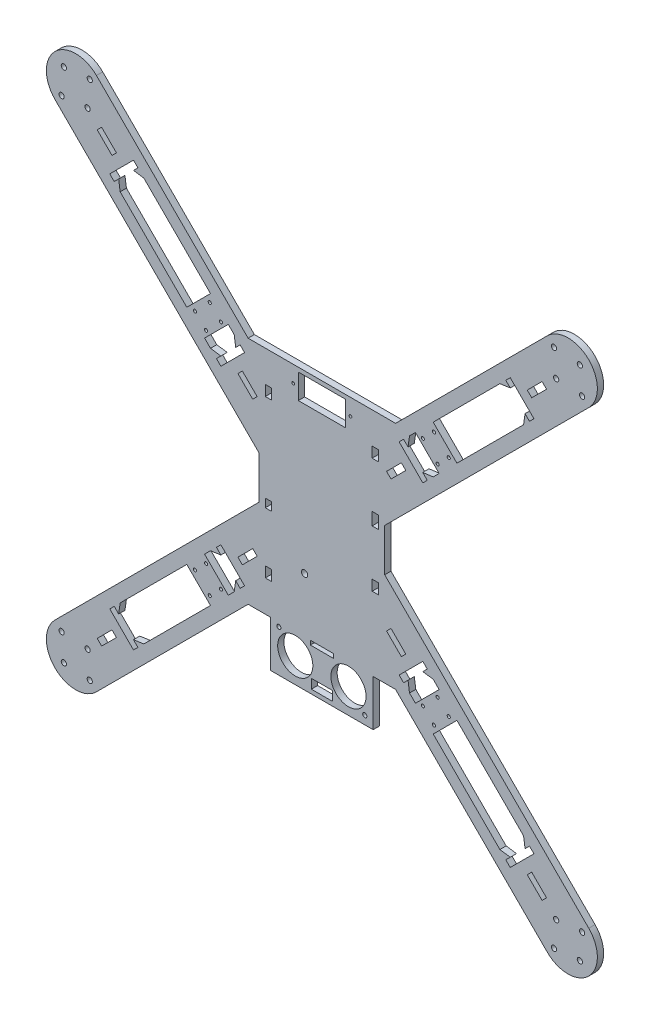
SolidWorks part; units mm, degrees
material "Custom Plastic"
ref_plane "Front Plane" through (0, 0, 0) normal (0, 0, 1) x (1, 0, 0)
ref_plane "Top Plane" through (0, 0, 0) normal (0, 1, 0) x (1, 0, 0)
ref_plane "Right Plane" through (0, 0, 0) normal (1, 0, 0) x (0, 0, -1)
sketch "Sketch1" plane through (0, 0, 0) normal (0, 0, 1) x (1, 0, 0)
  line L0 (117.5, 117.5) -> (-117.5, 117.5) construction
  line L1 (-117.5, 117.5) -> (117.5, -117.5) construction
  line L2 (117.5, -117.5) -> (-117.5, -117.5) construction
  line L3 (-117.5, -117.5) -> (117.5, 117.5) construction
  line L4 (117.5, 117.5) -> (117.5, -117.5) construction
  line L5 (-117.5, 117.5) -> (-117.5, -117.5) construction
  line L6 (0, 117.5) -> (0, -117.5) construction
  line L7 (35.201, 55) -> (-35.201, 55)
  line L8 (-30, 55) -> (30, 55) construction
  line L9 (-35.201, 55) -> (-107.6005, 127.3995)
  line L10 (-127.3995, 107.6005) -> (-30, 10.201)
  line L11 (-117.5, 0) -> (117.5, 0) construction
  line L12 (-30, 10.201) -> (-30, -10.201)
  line L13 (30, 55) -> (30, -55) construction
  line L14 (30, -55) -> (-30, -55) construction
  line L15 (-30, -55) -> (-30, 55) construction
  line L16 (30, 55) -> (-30, -55) construction
  line L17 (-24.5, -55) -> (-24.5, -77)
  line L18 (-127.3995, -107.6005) -> (-30, -10.201)
  line L19 (-24.5, -77) -> (24.5, -77)
  line L20 (-35.201, -55) -> (-107.6005, -127.3995)
  line L21 (35.201, -55) -> (24.5, -55)
  line L22 (35.201, -55) -> (107.6005, -127.3995)
  line L23 (127.3995, -107.6005) -> (30, -10.201)
  line L24 (30, 10.201) -> (30, -10.201)
  line L25 (127.3995, 107.6005) -> (30, 10.201)
  line L26 (35.201, 55) -> (107.6005, 127.3995)
  line L27 (24.5, -55) -> (24.5, -77)
  line L28 (-24.5, -55) -> (-35.201, -55)
  arc A0 (-107.6005, 127.3995) -> (-127.3995, 107.6005) centre (-117.5, 117.5) ccw
  arc A12 (-107.6005, -127.3995) -> (-127.3995, -107.6005) centre (-117.5, -117.5) cw
  arc A16 (107.6005, -127.3995) -> (127.3995, -107.6005) centre (117.5, -117.5) ccw
  arc A24 (107.6005, 127.3995) -> (127.3995, 107.6005) centre (117.5, 117.5) cw
  point P3 (0, 0)
  point P18 (0, 0)
  point P21 (0, -77)
  point P33 (-117.5, 117.5)
  point P34 (-30, 0)
  point P65 (0, -55)
  point P80 (0, 55)
  dimension "D3" = 14
  dimension "D8" = 24.5
  dimension "D7" = 22
  dimension "D1" = 235
  dimension "D2" = 235
  dimension "D4" = 60
  dimension "D5" = 110
  dimension "D6" = 28
extrude "Boss-Extrude1" add sketch "Sketch1" against normal blind 3
sketch "Sketch4" plane through (0, 0, 0) normal (0, 0, 1) x (1, 0, 0)
  line L0 (0, 0) -> (0, 55) construction
  line L1 (35.201, 55) -> (-35.201, 55) construction
  line L2 (0, 0) -> (-30, 0) construction
  line L3 (-30, 10.201) -> (-30, -10.201) construction
  line L4 (-30, 0) -> (-30, 10.201) construction
  line L5 (-30, 10.201) -> (-127.3995, 107.6005) construction
  line L6 (-35.201, 55) -> (-107.6005, 127.3995) construction
  line L7 (-107.6005, 127.3995) -> (-127.3995, 107.6005) construction
  line L8 (-110.7825, 124.2175) -> (-124.2175, 110.7825) construction
  line L9 (-123.1569, 123.1569) -> (-111.8431, 111.8431) construction
  circle A20 centre (-110.7825, 124.2175) radius 1.25
  circle A21 centre (-124.2175, 110.7825) radius 1.25
  circle A22 centre (-123.1569, 123.1569) radius 1.25
  circle A23 centre (-111.8431, 111.8431) radius 1.25
  circle A24 centre (111.8431, 111.8431) radius 1.25
  circle A25 centre (110.7825, 124.2175) radius 1.25
  circle A26 centre (123.1569, 123.1569) radius 1.25
  circle A27 centre (124.2175, 110.7825) radius 1.25
  circle A28 centre (111.8431, -111.8431) radius 1.25
  circle A29 centre (124.2175, -110.7825) radius 1.25
  circle A30 centre (123.1569, -123.1569) radius 1.25
  circle A31 centre (110.7825, -124.2175) radius 1.25
  circle A32 centre (-111.8431, -111.8431) radius 1.25
  circle A33 centre (-110.7825, -124.2175) radius 1.25
  circle A34 centre (-123.1569, -123.1569) radius 1.25
  circle A35 centre (-124.2175, -110.7825) radius 1.25
  point P16 (-117.5, 117.5)
  point P19 (-117.5, 117.5)
  point P26 (-117.5, 117.5)
  point P62 (0, 0)
  dimension "D4" = 2.5
  dimension "D2" = 19
  dimension "D3" = 16
extrude "Cut-Extrude1" cut sketch "Sketch4" against normal blind 3
sketch "Sketch5" plane through (0, 0, 0) normal (0, 0, 1) x (1, 0, 0)
  line L7 (-11.25, 53) -> (-11.25, 41.2)
  line L8 (-11.25, 41.2) -> (11.25, 41.2)
  line L9 (11.25, 41.2) -> (11.25, 53)
  line L10 (11.25, 53) -> (-11.25, 53)
  line L12 (0, 53) -> (0, 41.2) construction
  line L13 (-13.65, 47.1) -> (13.65, 47.1) construction
  line L14 (35.201, 55) -> (-35.201, 55) construction
  circle A2 centre (-13.65, 47.1) radius 0.65
  circle A3 centre (13.65, 47.1) radius 0.65
  point P20 (0, 47.1)
  point P21 (0, 47.1)
  point P26 (0, 55)
  dimension "D8" = 1.3
  dimension "D9" = 1.3
  dimension "D10" = 27.3
  dimension "D11" = 22.5
  dimension "D12" = 11.8
  dimension "D13" = 2
extrude "Cut-Extrude2" cut sketch "Sketch5" against normal blind 3
sketch "Sketch6" plane through (0, 0, 0) normal (0, 0, 1) x (1, 0, 0)
  line L1 (-11.25, 41.2) -> (11.25, 41.2) construction
  circle A0 centre (-8.25, -28.8) radius 1.5
  dimension "D3" = 3
  dimension "D1" = 70
  dimension "D2" = 3
extrude "Cut-Extrude3" cut sketch "Sketch6" against normal blind 3
sketch "Sketch7" plane through (0, 0, 0) normal (0, 0, 1) x (1, 0, 0)
  line L0 (-22.5, -55) -> (-22.5, -75) construction
  line L5 (-22.5, -75) -> (22.5, -75) construction
  line L6 (22.5, -75) -> (22.5, -55) construction
  line L7 (22.5, -55) -> (-22.5, -55) construction
  line L8 (0, -55) -> (0, -75) construction
  line L9 (-12.7, -65) -> (0, -65) construction
  line L10 (-24.5, -77) -> (24.5, -77) construction
  line L11 (-24.5, -55) -> (-24.5, -77) construction
  line L12 (-5.5, -55) -> (-5.5, -57)
  line L13 (-5.5, -57) -> (5.5, -57)
  line L15 (5.5, -55) -> (-5.5, -55)
  line L16 (-5, -75) -> (-5, -70.5)
  line L17 (-5, -70.5) -> (5, -70.5)
  line L21 (5, -75) -> (-5, -75)
  line L22 (5.5, -55) -> (5.5, -57)
  line L23 (5, -75) -> (5, -70.5)
  circle A5 centre (-20.5, -57) radius 1
  circle A6 centre (-12.7, -65) radius 8.4
  circle A7 centre (12.7, -65) radius 8.4
  circle A8 centre (20.5, -73) radius 1
  point P25 (0, -57)
  point P26 (0, -70.5)
  dimension "D3" = 2
  dimension "D6" = 20
  dimension "D13" = 5
  dimension "D5" = 45
  dimension "D1" = 2
  dimension "D4" = 16.8
  dimension "D14" = 2
  dimension "D2" = 2
  dimension "D7" = 2
  dimension "D8" = 2
  dimension "D9" = 12.7
  dimension "D10" = 5.5
  dimension "D11" = 2
  dimension "D12" = 4.5
  dimension "D15" = 2
  dimension "D16" = 2
extrude "Cut-Extrude4" cut sketch "Sketch7" against normal blind 3
sketch "Sketch8" plane through (0, 0, 0) normal (0, 0, 1) x (1, 0, 0)
  line L0 (101.2365, -89.9228) -> (89.9228, -101.2365)
  line L1 (89.9228, -101.2365) -> (87.8015, -99.1152)
  line L2 (36.8898, -48.2035) -> (48.2035, -36.8898)
  line L3 (48.2035, -36.8898) -> (50.3249, -39.0111)
  line L4 (105.4792, -85.6802) -> (85.6802, -105.4792) construction
  line L5 (127.3995, -107.6005) -> (30, -10.201) construction
  line L6 (35.201, -55) -> (107.6005, -127.3995) construction
  line L7 (40.0718, -37.9505) -> (37.9505, -40.0718)
  line L8 (115.8431, -107.8431) -> (111.8431, -111.8431) construction
  line L9 (37.9505, -40.0718) -> (30.8794, -33.0007)
  line L10 (50.3249, 39.0111) -> (48.2035, 36.8898)
  line L11 (30.8794, -33.0007) -> (33.0007, -30.8794)
  line L12 (33.0007, -30.8794) -> (40.0718, -37.9505)
  line L13 (42.5467, -42.5467) -> (39.0111, -39.0111) construction
  line L14 (35.201, -55) -> (107.6005, -127.3995) construction
  line L15 (100.1759, -98.0546) -> (98.0546, -100.1759)
  line L16 (98.0546, -100.1759) -> (105.1256, -107.247)
  line L17 (105.1256, -107.247) -> (107.247, -105.1256)
  line L18 (107.247, -105.1256) -> (100.1759, -98.0546)
  line L19 (99.1152, -99.1152) -> (95.5797, -95.5797) construction
  line L20 (-101.2365, -89.9228) -> (-99.1152, -87.8015)
  line L21 (-100.1759, -98.0546) -> (-107.247, -105.1256)
  line L22 (-107.247, -105.1256) -> (-105.1256, -107.247)
  line L23 (-105.1256, -107.247) -> (-98.0546, -100.1759)
  line L24 (-98.0546, -100.1759) -> (-100.1759, -98.0546)
  line L25 (-89.9228, -101.2365) -> (-101.2365, -89.9228)
  line L26 (-36.8898, -48.2035) -> (-39.0111, -50.3249)
  line L27 (-48.2035, -36.8898) -> (-36.8898, -48.2035)
  line L28 (-37.9505, -40.0718) -> (-40.0718, -37.9505)
  line L29 (-30.8794, -33.0007) -> (-37.9505, -40.0718)
  line L30 (-40.0718, -37.9505) -> (-33.0007, -30.8794)
  line L31 (-33.0007, -30.8794) -> (-30.8794, -33.0007)
  line L32 (-89.9228, 101.2365) -> (-87.8015, 99.1152)
  line L33 (-98.0546, 100.1759) -> (-105.1256, 107.247)
  line L34 (-105.1256, 107.247) -> (-107.247, 105.1256)
  line L35 (-107.247, 105.1256) -> (-100.1759, 98.0546)
  line L36 (-100.1759, 98.0546) -> (-98.0546, 100.1759)
  line L37 (-101.2365, 89.9228) -> (-89.9228, 101.2365)
  line L38 (-48.2035, 36.8898) -> (-50.3249, 39.0111)
  line L39 (-36.8898, 48.2035) -> (-48.2035, 36.8898)
  line L40 (-40.0718, 37.9505) -> (-37.9505, 40.0718)
  line L41 (-33.0007, 30.8794) -> (-40.0718, 37.9505)
  line L42 (-37.9505, 40.0718) -> (-30.8794, 33.0007)
  line L43 (-30.8794, 33.0007) -> (-33.0007, 30.8794)
  line L44 (101.2365, 89.9228) -> (99.1152, 87.8015)
  line L45 (100.1759, 98.0546) -> (107.247, 105.1256)
  line L46 (107.247, 105.1256) -> (105.1256, 107.247)
  line L47 (105.1256, 107.247) -> (98.0546, 100.1759)
  line L48 (98.0546, 100.1759) -> (100.1759, 98.0546)
  line L49 (89.9228, 101.2365) -> (101.2365, 89.9228)
  line L50 (36.8898, 48.2035) -> (39.0111, 50.3249)
  line L51 (48.2035, 36.8898) -> (36.8898, 48.2035)
  line L52 (37.9505, 40.0718) -> (40.0718, 37.9505)
  line L53 (30.8794, 33.0007) -> (37.9505, 40.0718)
  line L54 (40.0718, 37.9505) -> (33.0007, 30.8794)
  line L55 (33.0007, 30.8794) -> (30.8794, 33.0007)
  line L56 (30, 10.201) -> (127.3995, 107.6005) construction
  line L57 (41.8396, 53.1533) -> (84.9731, 96.2868)
  line L58 (96.2868, 84.9731) -> (53.1533, 41.8396)
  line L59 (87.8015, 99.1152) -> (89.9228, 101.2365)
  line L60 (99.1152, -87.8015) -> (96.9939, -89.9228)
  line L61 (-96.2868, -84.9731) -> (-53.1533, -41.8396)
  line L62 (96.9939, -89.9228) -> (96.2868, -84.9731)
  line L63 (99.1152, -87.8015) -> (101.2365, -89.9228)
  line L64 (87.8015, -99.1152) -> (89.9228, -96.9939)
  line L65 (-87.8015, -99.1152) -> (-89.9228, -101.2365)
  line L66 (89.9228, -96.9939) -> (84.9731, -96.2868)
  line L67 (84.9731, -96.2868) -> (41.8396, -53.1533)
  line L68 (50.3249, -39.0111) -> (48.2035, -41.1325)
  line L69 (48.2035, -41.1325) -> (53.1533, -41.8396)
  line L70 (53.1533, -41.8396) -> (96.2868, -84.9731)
  line L71 (39.0111, -50.3249) -> (41.1325, -48.2035)
  line L72 (41.1325, -48.2035) -> (41.8396, -53.1533)
  line L73 (39.0111, -50.3249) -> (36.8898, -48.2035)
  line L74 (-89.9228, -96.9939) -> (-84.9731, -96.2868)
  line L75 (-87.8015, -99.1152) -> (-89.9228, -96.9939)
  line L76 (-96.9939, -89.9228) -> (-96.2868, -84.9731)
  line L77 (-99.1152, -87.8015) -> (-96.9939, -89.9228)
  line L78 (-41.1325, -48.2035) -> (-41.8396, -53.1533)
  line L79 (-39.0111, -50.3249) -> (-41.1325, -48.2035)
  line L80 (-48.2035, -41.1325) -> (-53.1533, -41.8396)
  line L81 (-50.3249, -39.0111) -> (-48.2035, -41.1325)
  line L82 (-96.9939, 89.9228) -> (-96.2868, 84.9731)
  line L83 (-99.1152, 87.8015) -> (-96.9939, 89.9228)
  line L84 (-89.9228, 96.9939) -> (-84.9731, 96.2868)
  line L85 (-87.8015, 99.1152) -> (-89.9228, 96.9939)
  line L86 (-48.2035, 41.1325) -> (-53.1533, 41.8396)
  line L87 (-50.3249, 39.0111) -> (-48.2035, 41.1325)
  line L88 (-41.1325, 48.2035) -> (-41.8396, 53.1533)
  line L89 (-39.0111, 50.3249) -> (-41.1325, 48.2035)
  line L90 (89.9228, 96.9939) -> (84.9731, 96.2868)
  line L91 (87.8015, 99.1152) -> (89.9228, 96.9939)
  line L92 (96.9939, 89.9228) -> (96.2868, 84.9731)
  line L93 (99.1152, 87.8015) -> (96.9939, 89.9228)
  line L94 (41.1325, 48.2035) -> (41.8396, 53.1533)
  line L95 (39.0111, 50.3249) -> (41.1325, 48.2035)
  line L96 (48.1429, 41.1931) -> (53.1533, 41.8396)
  line L97 (50.3249, 39.0111) -> (48.1429, 41.1931)
  line L98 (-39.0111, 50.3249) -> (-36.8898, 48.2035)
  line L99 (-53.1533, 41.8396) -> (-96.2868, 84.9731)
  line L100 (-99.1152, 87.8015) -> (-101.2365, 89.9228)
  line L101 (-84.9731, 96.2868) -> (-41.8396, 53.1533)
  line L102 (-41.8396, -53.1533) -> (-84.9731, -96.2868)
  line L103 (-50.3249, -39.0111) -> (-48.2035, -36.8898)
  line L104 (96.2868, 84.9731) -> (84.9731, 96.2868) construction
  line L105 (53.1533, 41.8396) -> (41.8396, 53.1533) construction
  point P10 (95.5797, -95.5797)
  point P11 (95.5797, -95.5797)
  point P18 (-49.2642, 40.0718)
  point P19 (-49.2642, -40.0718)
  point P68 (0, 0)
  point P122 (0, 0)
  dimension "D1" = 23
  dimension "D2" = 75
  dimension "D3" = 3
  dimension "D4" = 10
  dimension "D5" = 5
  dimension "D6" = 6
  dimension "D7" = 3
  dimension "D8" = 10
  dimension "D9" = 5
  dimension "D11" = 6
  dimension "D12" = 3
  dimension "D13" = 4
  dimension "D14" = 3
  dimension "D15" = 3
  dimension "D16" = 4
  dimension "D17" = 3
  dimension "D18" = 3
  dimension "D19" = 4
  dimension "D20" = 3
  dimension "D21" = 3
  dimension "D22" = 4
  dimension "D23" = 3
  dimension "D24" = 3
  dimension "D25" = 4
  dimension "D26" = 3
  dimension "D27" = 4
  dimension "D28" = 3
  dimension "D29" = 3
  dimension "D30" = 4
  dimension "D31" = 4
  dimension "D32" = 3
  dimension "D33" = 3
  dimension "D34" = 4
  dimension "D35" = 4
  dimension "D36" = 3
  dimension "D37" = 3
  dimension "D38" = 4
  dimension "D39" = 4
  dimension "D40" = 3
  dimension "D41" = 3
  dimension "D42" = 4
  dimension "D43" = 4
  dimension "D10" = 4
extrude "Cut-Extrude5" cut sketch "Sketch8" against normal through all
sketch "Sketch9" plane through (-5.6569, 5.6569, 0) normal (0.7071, -0.7071, 0) x (0, 0, -1)
  line L0 (3, 128.1701) -> (3, 67.1701) construction
  line L1 (3, 83.1701) -> (0, 83.1701)
  line L2 (3, 83.1701) -> (3, 71.1701)
  line L3 (3, 71.1701) -> (0, 71.1701)
  line L4 (0, 83.1701) -> (0, 71.1701)
  line L5 (0, 128.1701) -> (0, 67.1701) construction
  line L6 (0, 0) -> (28.0274, 0) construction
  line L7 (3, 63.1701) -> (0, 63.1701) construction
  dimension "D1" = 8
  dimension "D2" = 12
extrude "Boss-Extrude2" add sketch "Sketch9" along normal up to next
sketch "Sketch11" plane through (5.6569, 5.6569, 0) normal (-0.7071, -0.7071, 0) x (0, 0, 1)
  line L0 (-3, -128.1701) -> (-3, -67.1701) construction
  line L1 (-3, -71.1701) -> (0, -71.1701)
  line L2 (-3, -71.1701) -> (-3, -83.1701)
  line L3 (-3, -83.1701) -> (0, -83.1701)
  line L4 (0, -71.1701) -> (0, -83.1701)
  line L5 (0, -128.1701) -> (0, -67.1701) construction
  line L6 (-3, -63.1701) -> (0, -63.1701) construction
  dimension "D1" = 8
  dimension "D2" = 12
extrude "Boss-Extrude3" add sketch "Sketch11" along normal up to next
sketch "Sketch12" plane through (5.6569, -5.6569, 0) normal (-0.7071, 0.7071, 0) x (0, 0, 1)
  line L0 (-3, -128.1701) -> (-3, -67.1701) construction
  line L1 (-3, -71.1701) -> (0, -71.1701)
  line L2 (-3, -71.1701) -> (-3, -83.1701)
  line L3 (-3, -83.1701) -> (0, -83.1701)
  line L4 (0, -71.1701) -> (0, -83.1701)
  line L5 (0, -128.1701) -> (0, -67.1701) construction
  dimension "D1" = 8
  dimension "D2" = 12
extrude "Boss-Extrude4" add sketch "Sketch12" along normal up to next
sketch "Sketch13" plane through (5.6569, 5.6569, 0) normal (-0.7071, -0.7071, 0) x (0, 0, 1)
  line L0 (-3, 67.1701) -> (-3, 128.1701) construction
  line L1 (-3, 71.1701) -> (0, 71.1701)
  line L2 (-3, 71.1701) -> (-3, 83.1701)
  line L3 (-3, 83.1701) -> (0, 83.1701)
  line L4 (0, 71.1701) -> (0, 83.1701)
  line L5 (0, 67.1701) -> (0, 128.1701) construction
  dimension "D1" = 8
  dimension "D2" = 12
extrude "Boss-Extrude5" add sketch "Sketch13" along normal up to next
sketch "Sketch14" plane through (0, 0, -3) normal (0, 0, -1) x (-1, 0, 0)
  line L0 (30, 0) -> (-30, 0) construction
  line L1 (30, 10.201) -> (30, -10.201) construction
  line L2 (-30, -10.201) -> (-30, 10.201) construction
  line L3 (25.5, -40) -> (25.5, 40) construction
  line L12 (24, -35) -> (-25.5, -35) construction
  line L13 (-25.5, -35) -> (-25.5, -15) construction
  line L14 (-24, 13) -> (-24, 7)
  line L17 (-24, 7) -> (-27, 7)
  line L19 (-24, 13) -> (-27, 13)
  line L23 (24, -40) -> (27, -40)
  line L24 (24, -40) -> (24, -35)
  line L25 (24, -35) -> (27, -35)
  line L26 (27, -40) -> (27, -35)
  line L27 (24, -11) -> (27, -11)
  line L28 (24, -11) -> (24, -7)
  line L29 (24, -7) -> (27, -7)
  line L30 (27, -11) -> (27, -7)
  line L31 (24, 35) -> (27, 35)
  line L32 (24, 35) -> (24, 40)
  line L33 (24, 40) -> (27, 40)
  line L34 (27, 35) -> (27, 40)
  line L35 (-27, 13) -> (-27, 7)
  line L37 (-24, -20) -> (-27, -20)
  line L38 (-24, -20) -> (-24, -15)
  line L39 (-24, -15) -> (-27, -15)
  line L40 (-27, -20) -> (-27, -15)
  line L41 (-24, 35) -> (-27, 35)
  line L42 (-24, 35) -> (-24, 40)
  line L43 (-24, 40) -> (-27, 40)
  line L44 (-27, 35) -> (-27, 40)
  point P11 (25.5, -40)
  point P16 (25.5, 0)
  point P28 (-25.5, 13)
  point P38 (-25.5, 7)
  dimension "D1" = 80
  dimension "D2" = 3
  dimension "D3" = 5
  dimension "D4" = 24
  dimension "D5" = 20
  dimension "D6" = 22
  dimension "D7" = 6
  dimension "D8" = 5
  dimension "D9" = 22
  dimension "D10" = 4
  dimension "D11" = 5
  dimension "D12" = 42
  dimension "D13" = 5
extrude "Cut-Extrude6" cut sketch "Sketch14" against normal through all
sketch "Sketch15" plane through (0, 0, -3) normal (0, 0, -1) x (-1, 0, 0)
  line L0 (-55.2746, -48.2035) -> (-48.2035, -55.2746) construction
  line L1 (-48.2035, -55.2746) -> (-53.5068, -60.5779) construction
  line L2 (-53.5068, -60.5779) -> (-60.5779, -53.5068) construction
  line L3 (-60.5779, -53.5068) -> (-55.2746, -48.2035) construction
  line L4 (-64.2902, -44.4912) -> (-44.4912, -64.2902) construction
  line L5 (-127.3995, -107.6005) -> (-30, -10.201) construction
  line L6 (-35.201, -55) -> (-107.6005, -127.3995) construction
  line L7 (-57.0424, -57.0424) -> (-51.7391, -51.7391) construction
  line L8 (-53.1533, -64.467) -> (-64.467, -53.1533) construction
  circle A6 centre (-60.5779, -53.5068) radius 0.75
  circle A7 centre (-55.2746, -48.2035) radius 0.75
  circle A8 centre (-48.2035, -55.2746) radius 0.75
  circle A9 centre (-53.5068, -60.5779) radius 0.75
  circle A10 centre (-53.5068, 60.5779) radius 0.75
  circle A11 centre (-48.2035, 55.2746) radius 0.75
  circle A12 centre (-60.5779, 53.5068) radius 0.75
  circle A13 centre (-55.2746, 48.2035) radius 0.75
  circle A14 centre (60.5779, 53.5068) radius 0.75
  circle A15 centre (55.2746, 48.2035) radius 0.75
  circle A16 centre (53.5068, 60.5779) radius 0.75
  circle A17 centre (48.2035, 55.2746) radius 0.75
  circle A18 centre (53.5068, -60.5779) radius 0.75
  circle A19 centre (48.2035, -55.2746) radius 0.75
  circle A20 centre (60.5779, -53.5068) radius 0.75
  circle A21 centre (55.2746, -48.2035) radius 0.75
  point P12 (-54.3907, -54.3907)
  point P19 (-54.3907, -54.3907)
  point P47 (0, 0)
  dimension "D3" = 1.5
  dimension "D1" = 7.5
  dimension "D2" = 10
  dimension "D4" = 2.5
  dimension "D5" = 4
extrude "Cut-Extrude7" cut sketch "Sketch15" against normal through all
